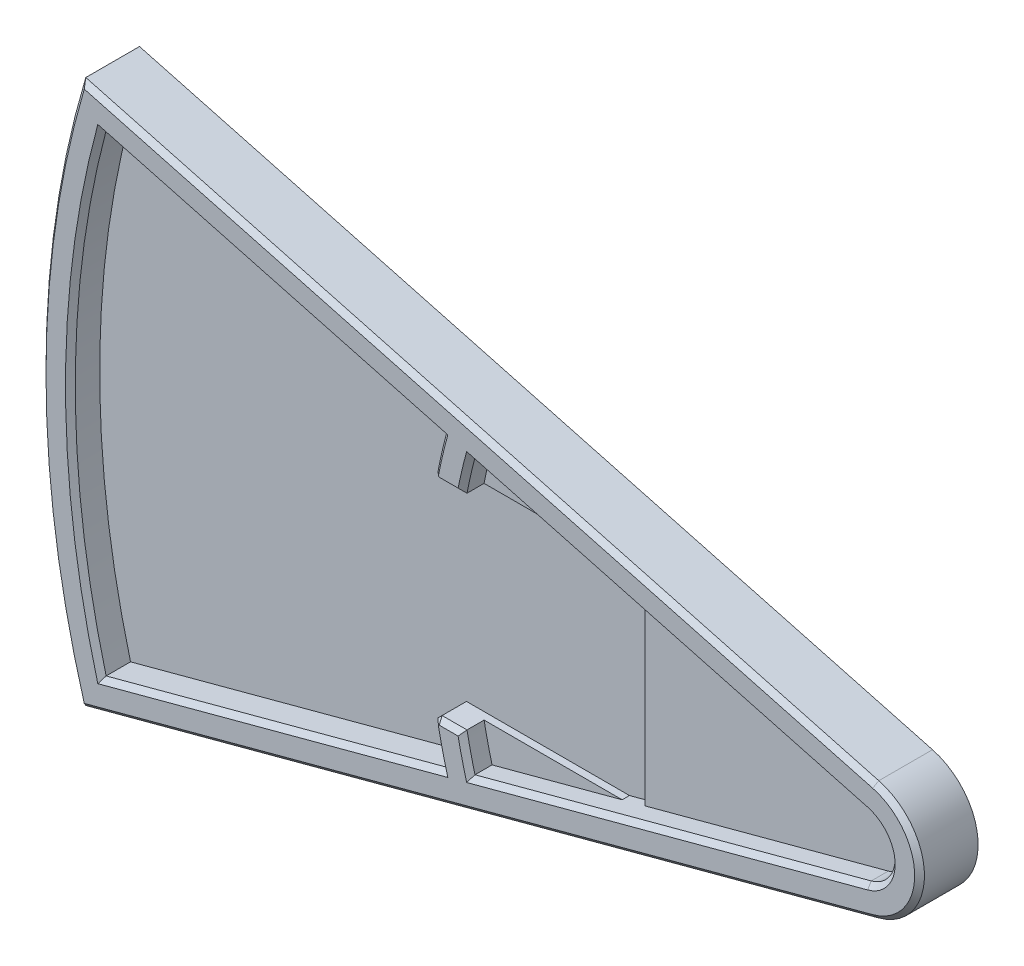
SolidWorks part; units mm, degrees
ref_plane "Front Plane" through (0, 0, 0) normal (0, 0, 1) x (1, 0, 0)
ref_plane "Top Plane" through (0, 0, 0) normal (0, 1, 0) x (1, 0, 0)
ref_plane "Right Plane" through (0, 0, 0) normal (1, 0, 0) x (0, 0, -1)
sketch "Sketch3" plane through (0, 0, 0) normal (0, 0, 1) x (1, 0, 0)
  line L0 (1.6782, 6.263) -> (-79.3962, 27.9868) construction
  line L1 (-79.3962, -27.9868) -> (1.6782, -6.263) construction
  line L2 (-1.4973, 0) -> (-50001.4973, 0) construction
  line L3 (-79.4865, -28.1425) -> (1.711, -6.3857)
  line L4 (1.711, 6.3857) -> (-79.4865, 28.1425)
  line L6 (3.264, 12.1813) -> (-159.2309, 55.7216)
  line L7 (3.264, 12.1813) -> (-83.598, 35.4558) construction
  line L8 (-83.598, -35.4558) -> (3.264, -12.1813) construction
  line L10 (3.264, -12.1813) -> (-83.598, -35.4558)
  line L11 (-159.2309, -55.7216) -> (-83.598, -35.4558)
  line L12 (-155.0666, -48.3941) -> (-85.1509, -29.6603)
  line L13 (-155.0666, 48.3941) -> (-85.1509, 29.6603)
  arc A0 (-79.3962, 27.9868) -> (-79.3962, -27.9868) centre (26.984, 0) ccw construction
  arc A1 (1.6782, -6.263) -> (1.6782, 6.263) centre (0, 0) ccw construction
  arc A2 (-79.4865, 28.1425) -> (-79.4865, -28.1425) centre (26.984, 0) ccw
  arc A3 (1.711, -6.3857) -> (1.711, 6.3857) centre (0, 0) ccw
  arc A4 (-85.2821, 29.6954) -> (-85.2821, -29.6954) centre (26.984, 0) ccw
  arc A5 (3.264, -12.1813) -> (3.264, 12.1813) centre (0, 0) ccw
  arc A6 (-159.2309, -55.7216) -> (-159.2309, 55.7216) centre (26.984, 0) cw
  arc A7 (-155.0666, -48.3941) -> (-155.0666, 48.3941) centre (26.984, 0) cw
  arc A8 (-155.0666, -48.3941) -> (-153.4827, 54.0016) centre (26.984, 0) cw construction
  arc A9 (-83.598, 35.4558) -> (-83.598, -35.4558) centre (26.984, 0) ccw construction
  point P8 (-83.016, 0)
  point P22 (-167.389, 0)
  point P24 (12.611, 0)
  point P26 (0, 0)
  dimension "D3" = 180
  dimension "D1" = 0.127
  dimension "D2" = 6
  dimension "D4" = 6
extrude "Boss-Extrude1" add sketch "Sketch3" along normal blind 6 contours L10 A5 L6 A6 L11
extrude "Boss-Extrude2" add sketch "Sketch3<3>" along normal blind 6 from surface contours A6 L11 L10 A5 L6 A3 L3 A2 L4 L12 A7 L13 A4 region at (10.4939, 0, 0) starting at face at (-77.6862, 0, 6)
sketch "Sketch3<3>" plane through (0, 0, 0) normal (0, 0, 1) x (1, 0, 0) same geometry as "Sketch3"
sketch "Sketch4" plane through (0, 0, 6) normal (0, 0, 1) x (1, 0, 0)
  line L11 (-52.8303, -21) -> (-81.1223, -21)
  line L12 (-49.0982, -20) -> (-79.0982, -20) construction
  line L13 (1.711, 6.3857) -> (-79.4865, 28.1425)
  line L14 (-79.4865, -28.1425) -> (1.711, -6.3857)
  line L15 (1.711, 6.3857) -> (-79.4865, 28.1425)
  line L16 (-79.4865, -28.1425) -> (1.711, -6.3857)
  line L17 (-49.0982, -20) -> (-49.0982, 20) construction
  line L18 (-49.0982, 20) -> (-79.0982, 20) construction
  line L19 (-79.0982, -20) -> (-79.0982, 20) construction
  line L20 (-49.0982, -20) -> (-79.0982, 20) construction
  line L21 (-49.0982, 20) -> (-79.0982, -20) construction
  line L22 (-48.0982, -19.7321) -> (-48.0982, 19.7321)
  line L23 (-52.8303, 21) -> (-81.1223, 21)
  line L24 (-48.0982, -21) -> (-79.0982, -21) construction
  line L25 (-48.0982, -21) -> (-48.0982, 21) construction
  line L26 (-48.0982, 21) -> (-79.0982, 21) construction
  arc A5 (1.711, -6.3857) -> (1.711, 6.3857) centre (0, 0) ccw
  arc A6 (-79.4865, 28.1425) -> (-79.4865, -28.1425) centre (26.984, 0) ccw
  arc A7 (1.711, -6.3857) -> (1.711, 6.3857) centre (0, 0) ccw
  arc A8 (-79.4865, 28.1425) -> (-79.4865, -28.1425) centre (26.984, 0) ccw
  point P16 (-64.0982, 0)
  point P27 (0, 0)
  point P28 (0, 0)
  arc M13 (1.711, -6.3857) -> (1.711, 6.3857) centre (0, 0) ccw
  line M14 (1.711, 6.3857) -> (-79.4865, 28.1425)
  arc M15 (-79.4865, 28.1425) -> (-79.4865, -28.1425) centre (26.984, 0) ccw
  line M16 (-79.4865, -28.1425) -> (1.711, -6.3857)
  dimension "D6" = 30
  dimension "D7" = 40
  dimension "D5" = 0
  dimension "D8" = 1
extrude "Boss-Extrude3" add sketch "Sketch4" along normal blind 1.5 contours L23 M14 M15 | L11 M16 M15 | L22 L16 M13 M14 region at (-71.1733, -23.3844, 6) region at (-26.3643, 0, 6) region at (-71.1733, 23.3844, 6)
sketch "Sketch5" plane through (0, 0, 6) normal (0, 0, 1) x (1, 0, 0)
  line L0 (0.52, 0) -> (-49999.48, 0) construction
  line L1 (-81.1223, 21) -> (-87.2285, 21)
  line L2 (-81.1223, -21) -> (-87.2285, -21)
  arc A0 (-85.2821, 29.6954) -> (-85.2821, -29.6954) centre (26.984, 0) ccw construction
  arc A1 (-85.2821, 29.6954) -> (-85.2821, -29.6954) centre (26.984, 0) ccw construction
  arc A2 (-81.1223, 21) -> (-81.1223, -21) centre (26.984, 0) ccw construction
  arc A3 (-87.2285, 21) -> (-87.2285, -21) centre (26.984, 0) ccw
  arc A4 (-81.1223, 21) -> (-81.1223, -21) centre (26.984, 0) ccw
extrude "Cut-Extrude3" cut sketch "Sketch5" along normal up to surface (6 mm away) up to face at (-122.7202, 0, 12)
chamfer "Chamfer1" distance 1 angle 45 2 edges at (-87.2285, -21, 9) (-87.2285, 21, 9) first distance on face at (-73.727, -21, 8.5) first distance on face at (-86.297, 25.3571, 9)
chamfer "Chamfer2" distance 1 angle 45 18 edges at (-80.3638, -24.5849, 12) (-38.8877, -17.2641, 12) (6.611, 0, 12) (-38.8877, 17.2641, 12) (-80.3638, 24.5849, 12) (-83.7459, 21, 12) (-86.7069, 21.4893, 12) (-86.2289, 25.852, 12) (-120.1743, 39.0448, 12) (-161.389, 0, 12) (-120.1743, -39.0448, 12) (-86.2444, -25.7842, 12) (-86.6495, -21.421, 12) (-83.6754, -21, 12) (-77.9835, -33.9514, 12) (-167.389, 0, 12) (-77.9835, 33.9514, 12) (12.611, 0, 12)
sketch "Sketch6" plane through (0, 0, 6) normal (0, 0, 1) x (1, 0, 0)
  line L0 (0, 0) -> (-50000, 0) construction
  line L1 (-85.2821, 29.6954) -> (-155.0666, 48.3941) construction
  line L3 (-104.7342, -7.6667) -> (-99.2288, -7.6667)
  line L4 (-104.7342, -7.6667) -> (-104.7342, 7.6667)
  line L5 (-104.7342, 7.6667) -> (-99.2288, 7.6667)
  line L6 (-99.2288, -7.6667) -> (-99.2288, 7.6667)
  line L7 (-104.7342, -7.6667) -> (-99.2288, 7.6667) construction
  line L8 (-104.7342, 7.6667) -> (-99.2288, -7.6667) construction
  arc A2 (-87.0704, -21.842) -> (-85.2821, -29.6954) centre (26.984, 0) ccw construction
  arc A3 (-85.2821, 29.6954) -> (-85.2821, -29.6954) centre (26.984, 0) ccw construction
  point P4 (-101.9815, 0)
  point P10 (-89.143, 0)
  dimension "D1" = 5.5053
